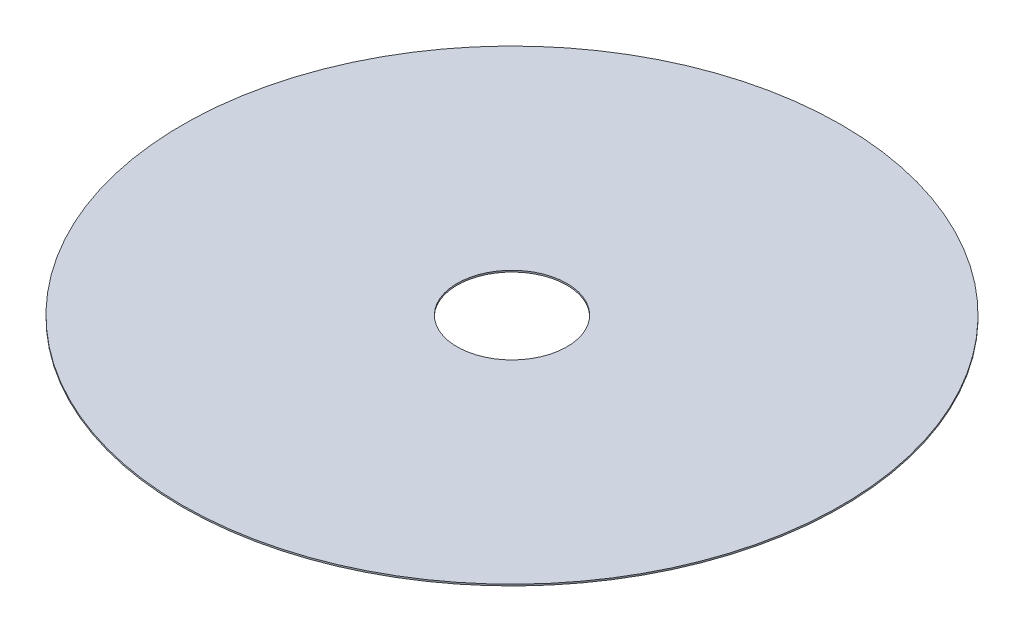
SolidWorks part; units mm, degrees
material "AISI 1020"
ref_plane "Front Plane" through (0, 0, 0) normal (0, 0, 1) x (1, 0, 0)
ref_plane "Top Plane" through (0, 0, 0) normal (0, 1, 0) x (1, 0, 0)
ref_plane "Right Plane" through (0, 0, 0) normal (1, 0, 0) x (0, 0, -1)
sketch "Sketch1" plane through (0, 0, 0) normal (0, 0, 1) x (1, 0, 0)
  line L0 (0, 0) -> (0, 30.5205) construction
  line L1 (0, 0) -> (250, 0)
  line L2 (250, 3.5) -> (250, -3.5)
  line L3 (250, 3.5) -> (1500, 3.5)
  line L4 (1500, 3.5) -> (1500, -3.5)
  line L5 (1500, -3.5) -> (250, -3.5)
  point P7 (250, 0)
revolve "Revolve1" add sketch "Sketch1" angle 360 about L0
sketch "Sketch2" plane through (0, 3.5, 0) normal (0, 1, 0) x (1, 0, 0)
  line L0 (0, -1460) -> (0, 1460)
  line L1 (-1460, 0) -> (1460, 0) construction
  line L2 (0, 0) -> (1348.8641, 558.7178) construction
  line L3 (0, 0) -> (558.7178, 1348.8641) construction
  line L4 (0, 0) -> (-1348.8641, 558.7178) construction
  line L5 (0, 0) -> (-558.7178, 1348.8641) construction
  line L6 (0, 0) -> (1348.8641, -558.7178) construction
  line L7 (0, 0) -> (558.7178, -1348.8641) construction
  line L8 (0, 0) -> (-1348.8641, -558.7178) construction
  line L9 (0, 0) -> (-558.7178, -1348.8641) construction
  arc A0 (1348.8641, 558.7178) -> (558.7178, 1348.8641) centre (0, 0) ccw construction
  circle A6 centre (0, 1460) radius 30 construction
  circle A8 centre (-1460, 0) radius 30 construction
  circle A9 centre (1460, 0) radius 30 construction
  circle A10 centre (0, -1460) radius 30 construction
  arc A11 (886.9244, 367.3761) -> (367.3761, 886.9244) centre (0, 0) ccw construction
  arc A12 (-1348.8641, 558.7178) -> (-558.7178, 1348.8641) centre (0, 0) cw construction
  arc A13 (-886.9244, 367.3761) -> (-367.3761, 886.9244) centre (0, 0) cw construction
  arc A14 (1348.8641, -558.7178) -> (558.7178, -1348.8641) centre (0, 0) cw construction
  arc A15 (886.9244, -367.3761) -> (367.3761, -886.9244) centre (0, 0) cw construction
  arc A16 (-1348.8641, -558.7178) -> (-558.7178, -1348.8641) centre (0, 0) ccw construction
  arc A17 (-886.9244, -367.3761) -> (-367.3761, -886.9244) centre (0, 0) ccw construction
  point P7 (0, 0)
  point P8 (0, 0)
